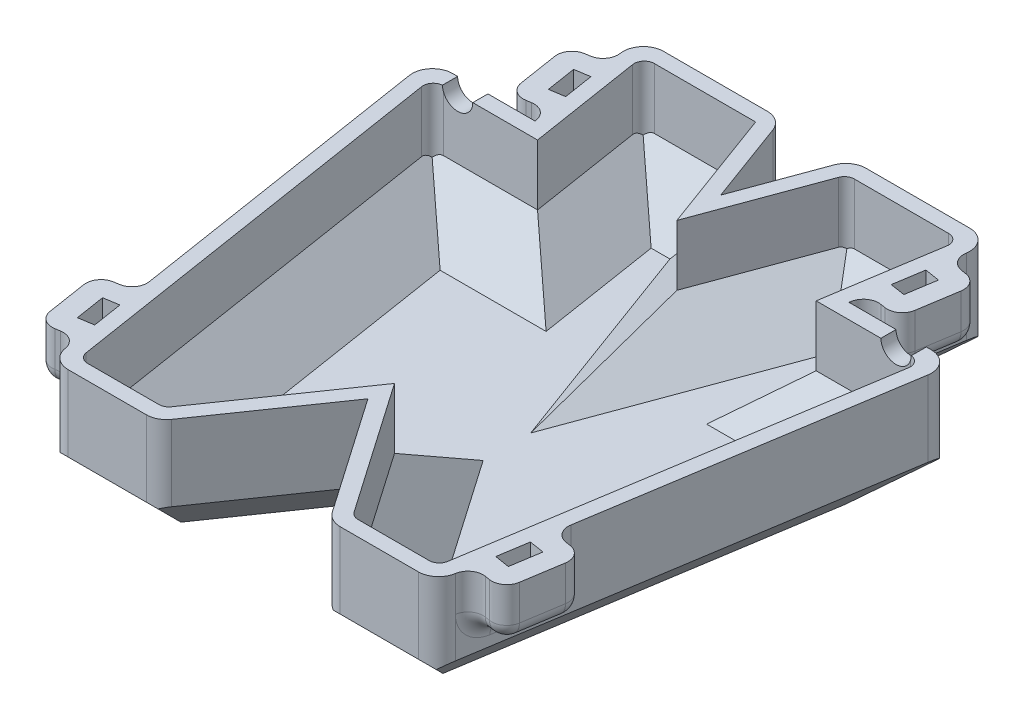
SolidWorks part; units mm, degrees
ref_plane "Front Plane" through (0, 0, 0) normal (0, 0, 1) x (1, 0, 0)
ref_plane "Top Plane" through (0, 0, 0) normal (0, 1, 0) x (1, 0, 0)
ref_plane "Right Plane" through (0, 0, 0) normal (1, 0, 0) x (0, 0, -1)
sketch "Sketch1" plane through (0, 0, 0) normal (0, 1, 0) x (1, 0, 0)
  line L0 (-35, 83.6369) -> (-7, 83.6369)
  line L1 (-7, 83.6369) -> (0, 64.6242)
  line L2 (-35, 83.6369) -> (-17.1111, -29.9632) construction
  line L3 (-14, 83.6369) -> (0, -5.2675) construction
  line L4 (0, 89.978) -> (0, -98.0426) construction
  line L5 (-48.6017, 55.9412) -> (-35.5466, -26.9632)
  line L6 (-31.1111, 58.9412) -> (-52.1111, 58.9412)
  line L7 (-17.1111, -29.9632) -> (-38.1111, -29.9632)
  line L8 (-52.1111, 58.9412) -> (-38.1111, -29.9632)
  line L9 (-35.5466, -26.9632) -> (-18.6822, -26.9632)
  line L10 (-18.6822, -26.9632) -> (0, 0)
  line L11 (0, -5.2675) -> (-17.1111, -29.9632)
  line L13 (14, 83.6369) -> (0, -5.2675) construction
  line L14 (0, -5.2675) -> (17.1111, -29.9632)
  line L17 (52.1111, 58.9412) -> (38.1111, -29.9632)
  line L18 (17.1111, -29.9632) -> (38.1111, -29.9632)
  line L19 (31.1111, 58.9412) -> (52.1111, 58.9412)
  line L20 (35, 83.6369) -> (17.1111, -29.9632) construction
  line L21 (7, 83.6369) -> (0, 64.6242)
  line L22 (35, 83.6369) -> (7, 83.6369)
  line L27 (0, 55.9412) -> (-9.0923, 80.6369)
  line L28 (-9.0923, 80.6369) -> (-31.4906, 80.6369)
  line L29 (-31.4906, 80.6369) -> (-27.6017, 55.9412)
  line L30 (-27.6017, 55.9412) -> (-48.6017, 55.9412)
  line L31 (18.6822, -26.9632) -> (0, 0)
  line L32 (35.5466, -26.9632) -> (18.6822, -26.9632)
  line L33 (48.6017, 55.9412) -> (35.5466, -26.9632)
  line L34 (27.6017, 55.9412) -> (48.6017, 55.9412)
  line L35 (31.4906, 80.6369) -> (27.6017, 55.9412)
  line L36 (9.0923, 80.6369) -> (31.4906, 80.6369)
  line L37 (0, 55.9412) -> (9.0923, 80.6369)
  line L38 (-35, 83.6369) -> (-31.1111, 58.9412)
  line L39 (35, 83.6369) -> (31.1111, 58.9412)
  line L40 (0, 0) -> (0, -5.2675)
  point P4 (-14, 83.6369)
  point P30 (14, 83.6369)
  dimension "D1" = 90
  dimension "D2" = 21
  dimension "D3" = 7
  dimension "D4" = 21
  dimension "D5" = 90
  dimension "D6" = 25
  dimension "D7" = 21
  dimension "D8" = 3
  dimension "D9" = 35
  dimension "D10" = 3
  dimension "D11" = 3
  dimension "D12" = 3
  dimension "D13" = 3
  dimension "D14" = 3
  dimension "D15" = 3
extrude "Boss-Extrude2" add sketch "Sketch1" along normal blind 25 contours L27 L37 L36 L35 L34 L33 L32 L31 L14 L18 L17 L19 L39 L22 L21 L1 L0 L38 L6 L8 L7 L11 L10 L9 L5 L30 L29 L28 region at (-21, 0, -82.0953)
extrude "Boss-Extrude5" add sketch "Sketch1<7>" along normal blind 3 contours L37 L27 L28 L29 L30 L5 L9 L10 L31 L32 L33 L34 L35 L36 region at (0, 0, -27.1018)
sketch "Sketch1<7>" plane through (0, 0, 0) normal (0, 1, 0) x (1, 0, 0) same geometry as "Sketch1"
chamfer "Chamfer2" distance 10 angle 45 28 edges at (27.1144, 3, 26.9632) (9.3411, 3, 13.4816) (-9.3411, 3, 13.4816) (-27.1144, 3, 26.9632) (42.0741, 3, -14.489) (38.1017, 3, -55.9412) (29.5462, 3, -68.2891) (20.2915, 3, -80.6369) (4.5462, 3, -68.2891) (-4.5462, 3, -68.2891) (-20.2915, 3, -80.6369) (-29.5462, 3, -68.2891) (-42.0741, 3, -14.489) (-38.1017, 3, -55.9412) (-3.5, 0, -74.1306) (3.5, 0, -74.1306) (21, 0, -83.6369) (33.0556, 0, -71.2891) (41.6111, 0, -58.9412) (45.1111, 0, -14.489) (27.6111, 0, 29.9632) (8.5556, 0, 17.6154) (-8.5556, 0, 17.6154) (-27.6111, 0, 29.9632) (-45.1111, 0, -14.489) (-41.6111, 0, -58.9412) (-33.0556, 0, -71.2891) (-21, 0, -83.6369)
fillet "Fillet4" radius 4 10 edges at (-38.1111, 17.5, 29.9632) (-17.1111, 17.5, 29.9632) (38.1111, 17.5, 29.9632) (17.1111, 17.5, 29.9632) (52.1111, 17.5, -58.9412) (35, 17.5, -83.6369) (7, 17.5, -83.6369) (-7, 17.5, -83.6369) (-52.1111, 17.5, -58.9412) (-35, 17.5, -83.6369)
fillet "Fillet5" radius 2 9 edges at (-18.6822, 19, 26.9632) (18.6822, 19, 26.9632) (35.5466, 19, 26.9632) (48.6017, 19, -55.9412) (31.4906, 19, -80.6369) (9.0923, 19, -80.6369) (-31.4906, 19, -80.6369) (-48.6017, 19, -55.9412) (-35.5466, 19, 26.9632)
sketch "Sketch5" plane through (-21.3013, 0, 3.3544) normal (-0.9878, 0, 0.1556) x (0.1556, 0, 0.9878)
  line L0 (-83.3841, 25) -> (-63.0633, 25) construction
  line L1 (-66.3841, 15) -> (-80.3841, 15)
  line L2 (-66.3841, 15) -> (-66.3841, 25)
  line L3 (-66.3841, 25) -> (-80.3841, 25)
  line L4 (-80.3841, 15) -> (-80.3841, 25)
  line L5 (-66.3841, 15) -> (-80.3841, 25) construction
  line L6 (-66.3841, 25) -> (-80.3841, 15) construction
  line L7 (-83.3841, 25) -> (-83.3841, 10) construction
  line L9 (-70.3841, 17.8571) -> (-76.3841, 17.8571) construction
  line L10 (-70.3841, 17.8571) -> (-70.3841, 22.1429) construction
  line L11 (-70.3841, 22.1429) -> (-76.3841, 22.1429) construction
  line L12 (-76.3841, 17.8571) -> (-76.3841, 22.1429) construction
  line L13 (-70.3841, 17.8571) -> (-76.3841, 22.1429) construction
  line L14 (-70.3841, 22.1429) -> (-76.3841, 17.8571) construction
  point P0 (-73.3841, 20)
  point P9 (-73.3841, 20)
  dimension "D1" = 14
  dimension "D2" = 10
  dimension "D3" = 3
  dimension "D4" = 6
extrude "Boss-Extrude6" add sketch "Sketch5" along normal blind 7
sketch "Sketch7" plane through (-41.7931, 0, 6.5813) normal (-0.9878, 0, 0.1556) x (0.1556, 0, 0.9878)
  line L0 (17.2507, 15) -> (3.2507, 15)
  line L1 (17.2507, 15) -> (17.2507, 25)
  line L2 (17.2507, 25) -> (3.2507, 25)
  line L3 (3.2507, 15) -> (3.2507, 25)
  line L4 (17.2507, 15) -> (3.2507, 25) construction
  line L5 (17.2507, 25) -> (3.2507, 15) construction
  line L6 (7.2507, 22.1429) -> (13.2507, 22.1429) construction
  line L7 (7.2507, 22.1429) -> (7.2507, 17.8571) construction
  line L8 (7.2507, 17.8571) -> (13.2507, 17.8571) construction
  line L9 (13.2507, 22.1429) -> (13.2507, 17.8571) construction
  line L10 (7.2507, 22.1429) -> (13.2507, 17.8571) construction
  line L11 (7.2507, 17.8571) -> (13.2507, 22.1429) construction
  line L12 (20.2507, 10) -> (20.2507, 25) construction
  line L13 (-61.6507, 25) -> (20.2507, 25) construction
  point P0 (10.2507, 20)
  point P5 (10.2507, 20)
  dimension "D1" = 14
  dimension "D2" = 10
  dimension "D3" = 6
  dimension "D4" = 3
extrude "Boss-Extrude7" add sketch "Sketch7" along normal blind 7
sketch "Sketch8" plane through (0, 25, 0) normal (0, 1, 0) x (1, 0, 0)
  line L0 (-36.1467, 71.6332) -> (-33.1832, 72.0999)
  line L1 (-36.1467, 71.6332) -> (-35.2134, 65.7063)
  line L2 (-33.1832, 72.0999) -> (-32.2499, 66.1729)
  line L3 (-35.2134, 65.7063) -> (-32.2499, 66.1729)
  line L4 (-43.6287, -14.2103) -> (-40.6652, -13.7437)
  line L5 (-43.6287, -14.2103) -> (-42.6954, -20.1373)
  line L6 (-40.6652, -13.7437) -> (-39.7319, -19.6706)
  line L7 (-42.6954, -20.1373) -> (-39.7319, -19.6706)
  line L8 (-34.2721, 79.0147) -> (-33.8055, 76.0512) construction
  line L9 (-40.7203, 74.9623) -> (-33.8055, 76.0512) construction
  line L10 (-51.3832, 54.319) -> (-41.2875, -9.7924) construction
  line L11 (-48.2023, -10.8813) -> (-41.2875, -9.7924) construction
  dimension "D1" = 4
  dimension "D2" = 4
  dimension "D3" = 3
  dimension "D4" = 6
extrude "Cut-Extrude1" cut sketch "Sketch8" against normal through all
ref_plane "Plane1" through (0, 0, 0) normal (-1, 0, 0) x (0, 0, 1)
mirror "Mirror1" about plane through (0, 0, 0) normal (-1, 0, 0) of "Cut-Extrude1", "Boss-Extrude7", "Boss-Extrude6"
fillet "Fillet6" radius 3 36 edges at (-39.1097, 20, 23.6219) (-40.9764, 15, 11.768) (-39.4208, 15, 21.6463) (-41.2875, 20, 9.7924) (-44.7449, 15, 10.3368) (-48.2023, 20, 10.8813) (-46.0245, 20, 24.7108) (-47.1134, 15, 17.796) (-42.5671, 15, 24.1664) (-33.8055, 20, -76.0512) (-31.6277, 20, -62.2216) (-38.5425, 20, -61.1327) (-40.7203, 20, -74.9623) (-37.2629, 15, -75.5068) (-33.4943, 15, -74.0756) (-39.6314, 15, -68.0475) (-31.9388, 15, -64.1973) (-35.0851, 15, -61.6772) (39.1097, 20, 23.6219) (41.2875, 20, 9.7924) (31.6277, 20, -62.2216) (33.8055, 20, -76.0512) (48.2023, 20, 10.8813) (46.0245, 20, 24.7108) (47.1134, 15, 17.796) (42.5671, 15, 24.1664) (39.4208, 15, 21.6463) (44.7449, 15, 10.3368) (40.9764, 15, 11.768) (40.7203, 20, -74.9623) (38.5425, 20, -61.1327) (39.6314, 15, -68.0475) (35.0851, 15, -61.6772) (31.9388, 15, -64.1973) (37.2629, 15, -75.5068) (33.4943, 15, -74.0756)
sketch "Sketch9" plane through (0, 0, -58.9412) normal (0, 0, -1) x (-1, 0, 0)
  line L1 (47.4319, 10) -> (47.4319, 25) construction
  line L3 (-47.4319, 25) -> (-47.4319, 10) construction
  line L4 (31.1111, 25) -> (47.4319, 25) construction
  line L5 (-31.1111, 25) -> (-47.4319, 25) construction
  circle A0 centre (43.4319, 25) radius 3
  circle A1 centre (-43.4319, 25) radius 3
  point P2 (0, 0)
  dimension "D1" = 6
  dimension "D4" = 6
  dimension "D3" = 4
  dimension "D6" = 4
extrude "Cut-Extrude2" cut sketch "Sketch9" against normal up to next
equation "\"D2@Sketch8\"=\"D1@Sketch8\""
